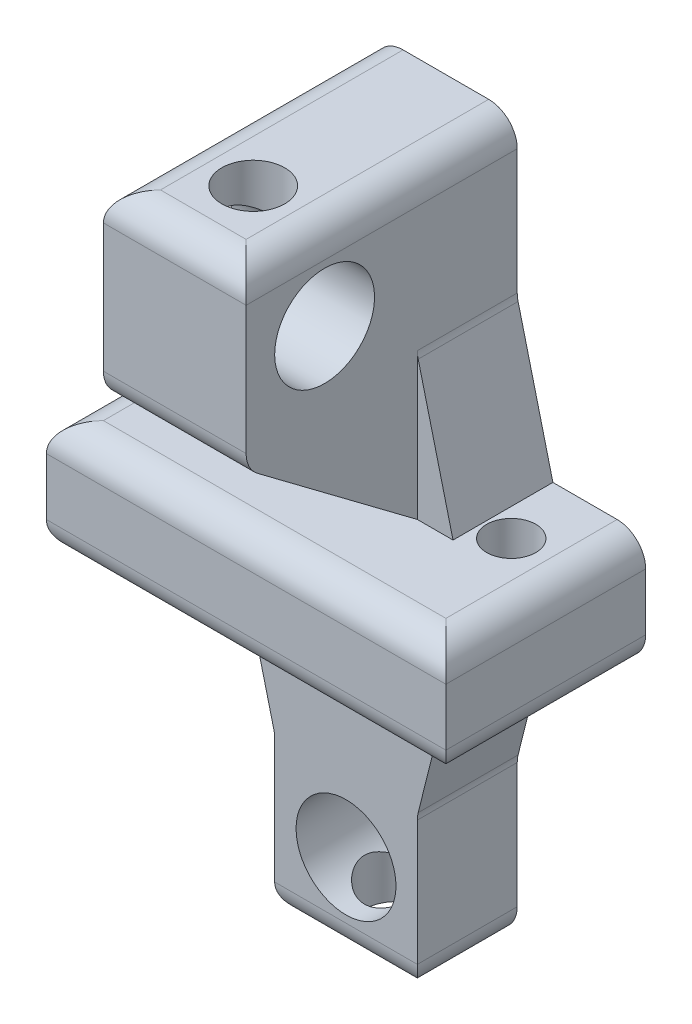
SolidWorks part; units mm, degrees
ref_plane "Front Plane" through (0, 0, 0) normal (0, 0, 1) x (1, 0, 0)
ref_plane "Top Plane" through (0, 0, 0) normal (0, 1, 0) x (1, 0, 0)
ref_plane "Right Plane" through (0, 0, 0) normal (1, 0, 0) x (0, 0, -1)
sketch "Sketch4" plane through (0, 0, 0) normal (0, 1, 0) x (1, 0, 0)
  line L1 (-2.5, -1.75) -> (2.5, -1.75)
  line L2 (-2.5, -1.75) -> (-2.5, 1.75)
  line L3 (-2.5, 1.75) -> (2.5, 1.75)
  line L4 (2.5, -1.75) -> (2.5, 1.75)
  line L5 (-2.5, -1.75) -> (2.5, 1.75) construction
  line L6 (-2.5, 1.75) -> (2.5, -1.75) construction
  point P0 (0, 0)
  dimension "D1" = 5
  dimension "D2" = 3.5
extrude "Boss-Extrude4" add sketch "Sketch4" along normal blind 25
sketch "Sketch5" plane through (0, 0, 0) normal (0, 0, 1) x (1, 0, 0)
  line L0 (0, 25) -> (0, 0) construction
  line L1 (-2.5, 25) -> (2.5, 25) construction
  line L2 (-2.5, 0) -> (2.5, 0) construction
  circle A0 centre (0, 3) radius 1.75
  dimension "D1" = 3
  dimension "D2" = 3.5
sketch "Sketch8" plane through (0, 0, 1.75) normal (0, 0, 1) x (1, 0, 0)
  line L0 (-2.5, 25) -> (-2.5, 0) construction
  line L1 (2.5, 19) -> (-2.5, 19)
  line L2 (2.5, 19) -> (2.5, 25)
  line L3 (2.5, 25) -> (-2.5, 25)
  line L4 (-2.5, 19) -> (-2.5, 25)
  line L5 (2.5, 19) -> (-2.5, 25) construction
  line L6 (2.5, 25) -> (-2.5, 19) construction
  line L7 (2.5, 25) -> (2.5, 0) construction
  point P0 (0, 22)
  dimension "D1" = 6
extrude "Boss-Extrude6" add sketch "Sketch8" along normal blind 6
sketch "Sketch9" plane through (0, 0, 0) normal (-1, 0, 0) x (0, 0, 1)
  line L1 (7.75, 22) -> (-1.75, 22) construction
  line L2 (7.75, 25) -> (7.75, 19) construction
  line L3 (-1.75, 25) -> (-1.75, 0) construction
  circle A0 centre (5, 22) radius 1.75
  dimension "D2" = 3.5
  dimension "D1" = 5
sketch "Sketch10" plane through (0, 0, 0) normal (1, 0, 0) x (0, 0, -1)
  line L0 (1.75, 25) -> (1.75, 0) construction
  line L1 (-5.25, 10.5) -> (1.75, 10.5)
  line L2 (-5.25, 10.5) -> (-5.25, 14.5)
  line L3 (-5.25, 14.5) -> (1.75, 14.5)
  line L4 (1.75, 10.5) -> (1.75, 14.5)
  line L5 (-5.25, 10.5) -> (1.75, 14.5) construction
  line L6 (-5.25, 14.5) -> (1.75, 10.5) construction
  line L7 (0, 25) -> (0, 0) construction
  line L8 (-7.75, 25) -> (1.75, 25) construction
  line L9 (1.75, 12.5) -> (-1.75, 12.5) construction
  point P0 (-1.75, 12.5)
  point P14 (0, 12.5)
  dimension "D1" = 4
  dimension "D2" = 7
extrude "Boss-Extrude8" add sketch "Sketch10" against normal blind 7 and the other way blind 7
sketch "Sketch11" plane through (0, 10.5, 0) normal (0, -1, 0) x (1, 0, 0)
  line L1 (-7, 5.25) -> (-7, -1.75) construction
  line L2 (-2.5, -1.75) -> (2.5, -1.75) construction
  line L8 (-7, 0) -> (7, 0) construction
  line L9 (0, 5.25) -> (0, -1.75) construction
  line L10 (-7, 5.25) -> (7, 5.25) construction
  line L13 (7, 5.25) -> (7, -1.75) construction
  circle A0 centre (-5.3, 2.3) radius 0.86
  circle A1 centre (4.72, 0.68) radius 0.86
  dimension "D1" = 1.72
  dimension "D2" = 2.3
  dimension "D4" = 1.72
  dimension "D5" = 0.68
  dimension "D6" = 4.72
  dimension "D3" = 5.3
extrude "Cut-Extrude1" cut sketch "Sketch11" against normal up to next
extrude "Cut-Extrude3" cut sketch "Sketch5" against normal up to next and the other way up to next
extrude "Cut-Extrude2" cut sketch "Sketch9" along normal up to next and the other way up to next
sketch "Sketch13" plane through (0, 25, 0) normal (0, 1, 0) x (1, 0, 0)
  line L0 (0, 0) -> (0, -5) construction
  circle A0 centre (0, -5) radius 1.1
  dimension "D2" = 2.2
  dimension "D1" = 5
extrude "Cut-Extrude4" cut sketch "Sketch13" against normal up to next
sketch "Sketch14" plane through (0, 0, 0) normal (0, -1, 0) x (1, 0, 0)
  circle A0 centre (0, 0) radius 1.1
  dimension "D1" = 2.2
extrude "Cut-Extrude5" cut sketch "Sketch14" against normal up to next
sketch "Sketch19" plane through (-2.5, 0, 0) normal (-1, 0, 0) x (0, 0, 1)
  line L0 (1.75, 14.5) -> (7.75, 19)
  line L1 (-1.75, 14.5) -> (5.25, 14.5) construction
rib "Rib5" sketch "Sketch19" sketch "Sketch19" thickness 5 extrusion direction parallel to sketch draft on no parameters "D1"=5
sketch "Sketch20" plane through (0, 0, -1.75) normal (0, 0, -1) x (-1, 0, 0)
  line L0 (2.5, 19.5) -> (3.75, 14.5)
  line L1 (2.5, 25) -> (2.5, 14.5) construction
  line L2 (2.5, 14.5) -> (7, 14.5) construction
  dimension "D1" = 1.25
  dimension "D2" = 5
rib "Rib8" sketch "Sketch20" sketch "Sketch20" thickness 3.5 extrusion direction parallel to sketch draft on no parameters "D1"=3.5
sketch "Sketch21" plane through (0, 0, -1.75) normal (0, 0, -1) x (-1, 0, 0)
  line L0 (3.75, 10.5) -> (2.5, 5.5)
  line L1 (2.5, 10.5) -> (7, 10.5) construction
  line L2 (2.5, 10.5) -> (2.5, 0) construction
  dimension "D1" = 1.25
  dimension "D2" = 5
rib "Rib9" sketch "Sketch21" sketch "Sketch21" thickness 3.5 extrusion direction parallel to sketch draft on no parameters "D1"=3.5
mirror "Mirror3" about plane through (0, 0, 0) normal (1, 0, 0) of "Rib8", "Rib9"
fillet "Fillet2" radius 1 17 edges at (2.5, 25, 3) (-2.5, 25, 3) (0, 25, 7.75) (-2.5, 19.5, 0) (2.5, 19.5, 0) (0, 19, 7.75) (0, 14.5, 5.25) (7, 14.5, 1.75) (7, 10.5, 1.75) (0, 10.5, 5.25) (-7, 14.5, 1.75) (-7, 10.5, 1.75) (-2.5, 5.5, 0) (0, 0, 1.75) (-2.5, 0, 0) (2.5, 5.5, 0) (2.5, 0, 0)
